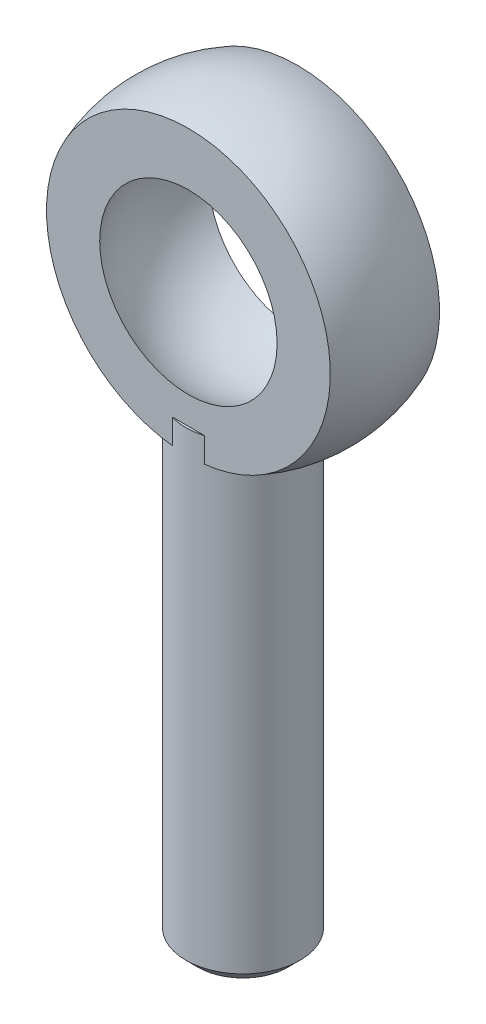
SolidWorks part; units mm, degrees
material "Plain Carbon Steel"
ref_plane "Front Plane" through (0, 0, 0) normal (0, 0, 1) x (1, 0, 0)
ref_plane "Top Plane" through (0, 0, 0) normal (0, 1, 0) x (1, 0, 0)
ref_plane "Right Plane" through (0, 0, 0) normal (1, 0, 0) x (0, 0, -1)
sketch "Sketch2" plane through (0, 0, 0) normal (1, 0, 0) x (0, 0, -1)
  line L0 (0, 15.4744) -> (0, -15.7624) construction
  line L1 (0, 8.7) -> (0, -8.7)
  arc A0 (0, 8.7) -> (0, -8.7) centre (0, 0) cw
  point P6 (0, -14.2606)
  dimension "D1" = 8.7
sketch "Sketch3" plane through (0, 0, 0) normal (1, 0, 0) x (0, 0, -1)
  line L0 (-8.1466, 0) -> (8.1466, 0) construction
  line L1 (0, 31.115) -> (0, -31.115) construction
  line L2 (-4.56, 11.8531) -> (-4.56, 0)
  line L3 (-4.56, 0) -> (4.56, 0)
  line L4 (4.56, 0) -> (4.56, 11.8531)
  arc A0 (-4.56, 11.8531) -> (4.56, 11.8531) centre (0, 0) cw
  point P8 (0, 12.7)
  dimension "D2" = 9.12
  dimension "D1" = 12.7
revolve "Revolve2" add sketch "Sketch3"
revolve "Cut-Revolve2" cut sketch "Sketch2" angle 360 about L0
sketch "Sketch4" plane through (0, 0, 0) normal (1, 0, 0) x (0, 0, -1)
  line L0 (0, -12.7) -> (0, -35.6534) construction
  arc A0 (-4.56, -11.8531) -> (4.56, -11.8531) centre (0, 0) ccw construction
ref_plane "Plane1" through (0, -12.7, 0) normal (0, 1, 0) x (-1, 0, 0)
sketch "Sketch5" plane through (0, -12.7, 0) normal (0, 1, 0) x (-1, 0, 0)
  circle A0 centre (0, 0) radius 4.7625
  dimension "D1" = 9.525
extrude "Extrude2" add sketch "Sketch5" against normal blind 36.53 and the other way blind 3 separate body
cosmetic thread "Cosmetic Thread1" parameters "D1"=31.75, "D2"=7.1438
chamfer "Chamfer1" distance 1 angle 45 1 edges at (0, -49.23, 4.7625)
sketch "Sketch6" plane through (0, 0, 0) normal (1, 0, 0) x (0, 0, -1)
  line L0 (0, 18.0632) -> (0, -54.6469) construction
  line L1 (10.0987, 0) -> (-10.0987, 0) construction
  line L2 (0, -12.7) -> (0, -35.6534) construction
  line L3 (-3.7625, -49.23) -> (3.7625, -49.23) construction
  point P5 (0, 0)
  point P6 (0, -33.23)
  dimension "D1" = 16
